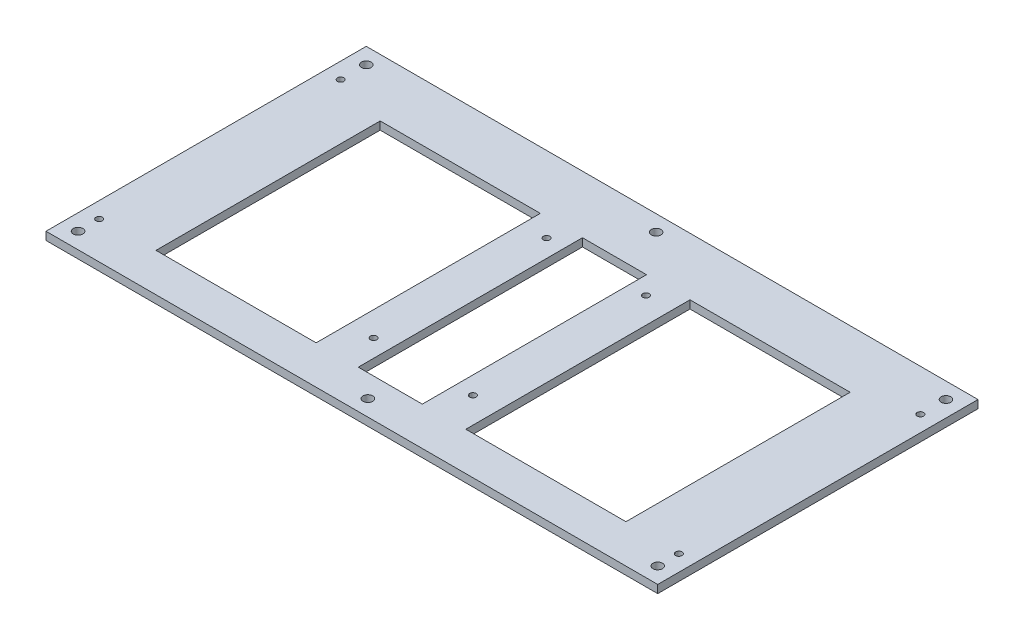
SolidWorks part; units mm, degrees
ref_plane "Front Plane" through (0, 0, 0) normal (0, 0, 1) x (1, 0, 0)
ref_plane "Top Plane" through (0, 0, 0) normal (0, 1, 0) x (1, 0, 0)
ref_plane "Right Plane" through (0, 0, 0) normal (1, 0, 0) x (0, 0, -1)
sketch "Sketch1" plane through (0, 0, 0) normal (0, 1, 0) x (1, 0, 0)
  line L0 (191, 106) -> (-191, 106)
  line L7 (-191, -94) -> (191, -94)
  line L8 (-191, -94) -> (-191, 106)
  line L10 (191, -94) -> (191, 106)
  dimension "D1" = 200
  dimension "D2" = 94
  dimension "D3" = 382
  dimension "D4" = 191
extrude "Boss-Extrude5" add sketch "Sketch1" along normal blind 5 contours L7 L10 L0 L8 region at (0, 0, -6)
sketch "Sketch7" plane through (0, 5, 0) normal (0, 1, 0) x (1, 0, 0)
  line L0 (191, -94) -> (191, 106) construction
  line L1 (-191, -94) -> (-191, 106) construction
  line L6 (191, 106) -> (-191, 106) construction
  circle A3 centre (181, 80) radius 2
  circle A4 centre (181, -70.8) radius 2
  circle A5 centre (31, 58.6) radius 2
  circle A6 centre (-31, 58.6) radius 2
  circle A7 centre (-181, 80) radius 2
  circle A8 centre (-181, -70.8) radius 2
  circle A9 centre (31, -49.4) radius 2
  circle A10 centre (-31, -49.4) radius 2
  dimension "D2" = 26
  dimension "D3" = 4
  dimension "D6" = 21.4
  dimension "D13" = 4
  dimension "D14" = 4
  dimension "D15" = 4
  dimension "D4" = 4
  dimension "D5" = 4
  dimension "D7" = 150
  dimension "D11" = 10
  dimension "D12" = 150.8
  dimension "D17" = 21.4
  dimension "D18" = 150.8
  dimension "D10" = 150
  dimension "D8" = 21.4
  dimension "D9" = 150
  dimension "D20" = 4
  dimension "D21" = 10
  dimension "D22" = 10
  dimension "D23" = 150
  dimension "D24" = 4
  dimension "D25" = 10
  dimension "D16" = 21.4
  dimension "D19" = 26
extrude "Cut-Extrude4" cut sketch "Sketch7" against normal blind 5
sketch "Sketch8" plane through (0, 5, 0) normal (0, 1, 0) x (1, 0, 0)
  line L1 (-20, 70) -> (20, 70)
  line L2 (-20, 70) -> (-20, -70)
  line L3 (-20, -70) -> (20, -70)
  line L4 (20, 70) -> (20, -70)
  line L5 (-20, 70) -> (20, -70) construction
  line L6 (-20, -70) -> (20, 70) construction
  line L7 (47.1549, 70) -> (147.1549, 70)
  line L8 (47.1549, 70) -> (47.1549, -70)
  line L9 (47.1549, -70) -> (147.1549, -70)
  line L10 (147.1549, 70) -> (147.1549, -70)
  line L11 (47.1549, 70) -> (147.1549, -70) construction
  line L12 (47.1549, -70) -> (147.1549, 70) construction
  line L13 (-46.3181, 70) -> (-146.3181, 70)
  line L14 (-46.3181, 70) -> (-46.3181, -70)
  line L15 (-46.3181, -70) -> (-146.3181, -70)
  line L16 (-146.3181, 70) -> (-146.3181, -70)
  line L17 (-46.3181, 70) -> (-146.3181, -70) construction
  line L18 (-46.3181, -70) -> (-146.3181, 70) construction
  point P0 (0, 0)
  point P6 (97.1549, 0)
  point P11 (-96.3181, 0)
  dimension "D1" = 40
  dimension "D2" = 140
  dimension "D3" = 140
  dimension "D4" = 140
  dimension "D5" = 0
  dimension "D6" = 0
  dimension "D7" = 100
  dimension "D8" = 100
extrude "Cut-Extrude5" cut sketch "Sketch8" against normal blind 10
sketch "Sketch9" plane through (0, 5, 0) normal (0, 1, 0) x (1, 0, 0)
  line L0 (191, 106) -> (-191, 106) construction
  line L1 (191, -94) -> (191, 106) construction
  line L2 (-191, -94) -> (191, -94) construction
  line L3 (-191, -94) -> (-191, 106) construction
  circle A0 centre (181, 96) radius 3
  circle A1 centre (181, -84) radius 3
  circle A2 centre (-181, 96) radius 3
  circle A3 centre (-181, -84) radius 3
  circle A4 centre (0, 96) radius 3
  circle A5 centre (0, -84) radius 3
  dimension "D9" = 6
  dimension "D10" = 6
  dimension "D11" = 6
  dimension "D12" = 6
  dimension "D13" = 6
  dimension "D16" = 6
  dimension "D18" = 181
  dimension "D1" = 10
  dimension "D2" = 10
  dimension "D3" = 10
  dimension "D4" = 10
  dimension "D5" = 10
  dimension "D6" = 10
  dimension "D7" = 10
  dimension "D8" = 10
  dimension "D14" = 181
  dimension "D15" = 10
  dimension "D17" = 10
extrude "Cut-Extrude6" cut sketch "Sketch9" against normal blind 10
